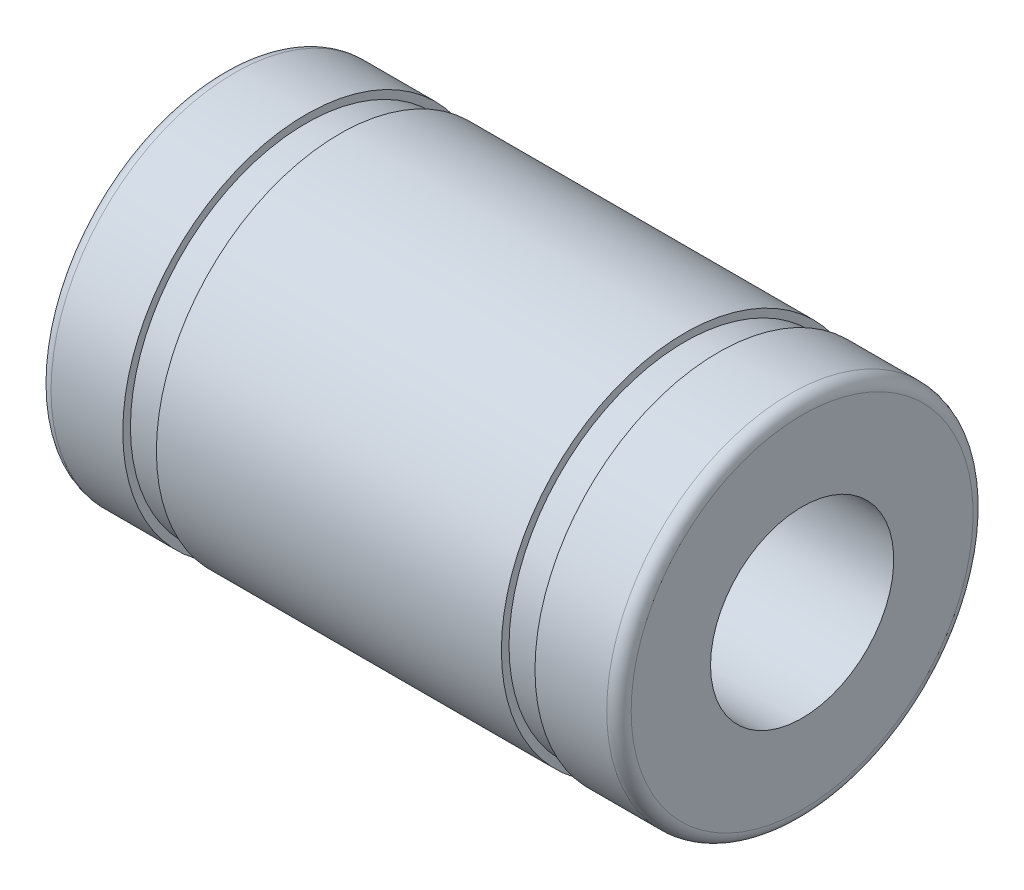
SolidWorks part; units mm, degrees
ref_plane "Front Plane" through (0, 0, 0) normal (0, 0, 1) x (1, 0, 0)
ref_plane "Top Plane" through (0, 0, 0) normal (0, 1, 0) x (1, 0, 0)
ref_plane "Right Plane" through (0, 0, 0) normal (1, 0, 0) x (0, 0, -1)
sketch "Sketch1" plane through (0, 0, 0) normal (0, 0, 1) x (1, 0, 0)
  line L0 (0, 5.6) -> (0, 3)
  line L1 (0, 3) -> (19, 3)
  line L2 (19, 3) -> (19, 5.6)
  line L3 (18.6, 6) -> (16.25, 6)
  line L4 (16.25, 6) -> (16.25, 5.75)
  line L5 (16.25, 5.75) -> (15.15, 5.75)
  line L6 (15.15, 5.75) -> (15.15, 6)
  line L7 (15.15, 6) -> (3.85, 6)
  line L8 (3.85, 6) -> (3.85, 5.75)
  line L9 (3.85, 5.75) -> (2.75, 5.75)
  line L10 (2.75, 5.75) -> (2.75, 6)
  line L11 (2.75, 6) -> (0.4, 6)
  line L12 (19, 0) -> (0, 0) construction
  arc A0 (19, 5.6) -> (18.6, 6) centre (18.6, 5.6) ccw
  arc A1 (0.4, 6) -> (0, 5.6) centre (0.4, 5.6) ccw
revolve "Revolve1" add sketch "Sketch1" angle 360 about L12 reverse direction yes
ref_plane "Plane1" through (9.5, 0, 0) normal (1, 0, 0) x (0, 0, -1)
ref_plane "bushing XY" through (9.5, 0, 0) normal (1, 0, 0) x (0, 0, -1)
ref_plane "bushing XZ" through (0, 0, 0) normal (0, -1, 0) x (-1, 0, 0)
ref_plane "bushing YZ" through (0, 0, 0) normal (0, 0, -1) x (-1, 0, 0)
ref_axis "bushing X" through (9.5, 0, 80.9) along (0, 0, -1)
ref_axis "bushing Y" through (9.5, -50, 0) along (0, 1, 0)
ref_axis "bushing Z" through (80.9, 0, 0) along (-1, 0, 0)
sketch3d "bushing"
  point P0 (9.5, 0, 0)
